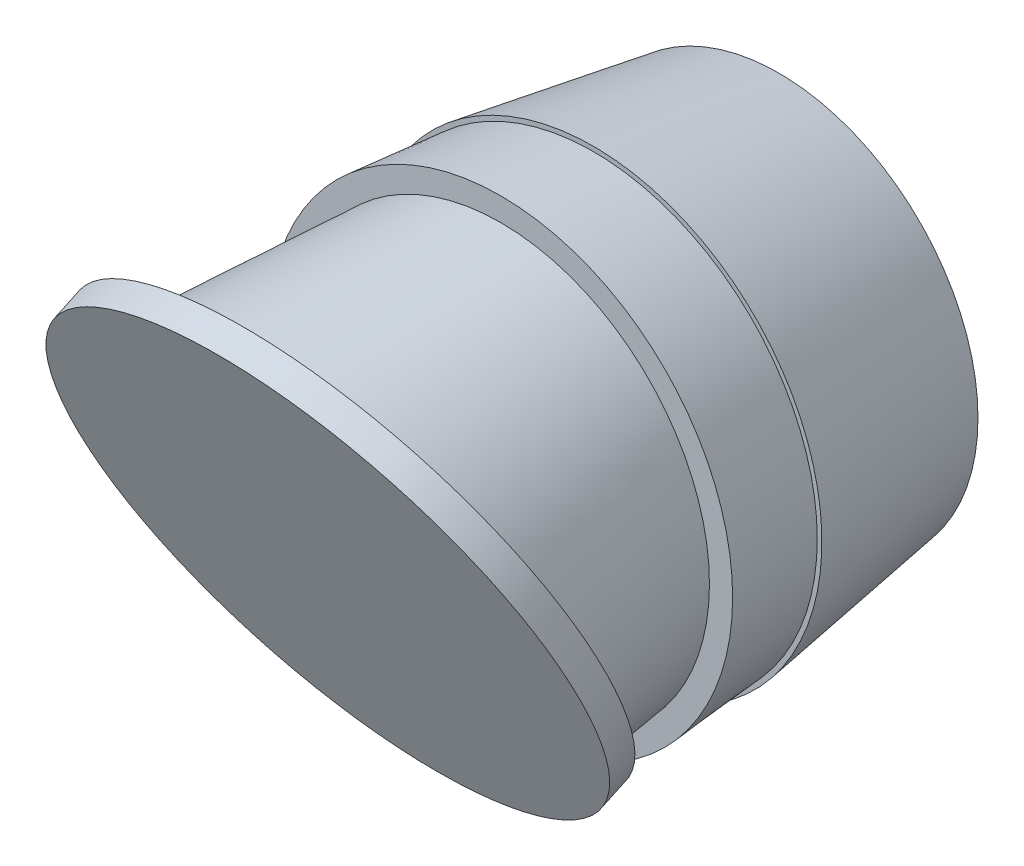
SolidWorks part; units mm, degrees
ref_plane "Front Plane" through (0, 0, 0) normal (0, 0, 1) x (1, 0, 0)
ref_plane "Top Plane" through (0, 0, 0) normal (0, 1, 0) x (1, 0, 0)
ref_plane "Right Plane" through (0, 0, 0) normal (1, 0, 0) x (0, 0, -1)
sketch "Sketch1" plane through (0, 0, 0) normal (0, 0, 1) x (1, 0, 0)
  line L0 (0, 34.9907) -> (0, -37.6588) construction
  line L1 (-13.89, -40) -> (14.3357, -40) construction
  circle A0 centre (0, 0) radius 22.5
  circle A1 centre (0, 0) radius 25
  point P8 (0, 22.5)
  dimension "D1" = 45
  dimension "D3" = 50
  dimension "D2" = 40
sketch "Sketch2" plane through (0, 0, 0) normal (1, 0, 0) x (0, 0, -1)
  line L0 (-19.9862, 0) -> (11.8569, 0) construction
ref_plane "Plane1" through (0, -7.1442, 15.3209) normal (0, -0.4226, 0.9063) x (1, 0, 0)
sketch "Sketch3" plane through (0, -7.1442, 15.3209) normal (0, -0.4226, 0.9063) x (1, 0, 0)
  line L0 (0, 7.8828) -> (0, 47.8828)
  line L2 (0, 19.9432) -> (0, -19.0864) construction
  circle A0 centre (0, 7.8828) radius 25
  circle A1 centre (0, 7.8828) radius 28
  circle A2 centre (0, 7.8828) radius 4.1
  circle A3 centre (0, 7.8828) radius 5
  circle A4 centre (0, 7.8828) radius 1.5
  point P4 (0, 32.8828)
  dimension "D1" = 50
  dimension "D2" = 3
  dimension "D4" = 3
  dimension "D5" = 8.2
  dimension "D6" = 10
  dimension "D3" = 40
extrude "Boss-Extrude1" add sketch "Sketch1" against normal blind 10 draft 5 contours A1
sketch "Sketch4" plane through (0, 0, -10) normal (0, 0, -1) x (-1, 0, 0)
  circle A1 centre (0, 0) radius 24.1251 construction
  circle A3 centre (0, 0) radius 24.1251 construction
  circle A4 centre (0, 0) radius 24.6251
  dimension "D1" = 0.5
extrude "Boss-Extrude2" add sketch "Sketch4" along normal blind 20 draft 9
loft "Loft2" add section "Sketch3" section "Sketch1<38>" connector at (-0.0458, 22.6577, 29.2177) connector at (0.0682, 22.4999, 0)
sketch "Sketch1<38>" plane through (0, 0, 0) normal (0, 0, 1) x (1, 0, 0) same geometry as "Sketch1"
extrude "Boss-Extrude4" add sketch "Sketch3<7>" against normal blind 3 contours A1
sketch "Sketch3<7>" plane through (0, -7.1442, 15.3209) normal (0, -0.4226, 0.9063) x (1, 0, 0) same geometry as "Sketch3"
